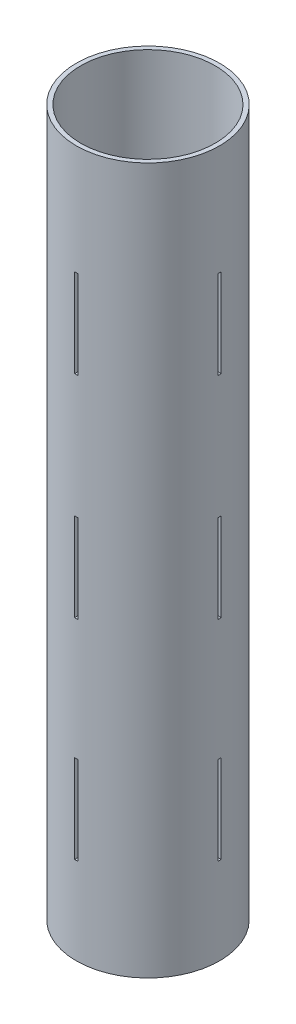
SolidWorks part; units mm, degrees
material "7075-T6 (SN)"
ref_plane "Front Plane" through (0, 0, 0) normal (0, 0, 1) x (1, 0, 0)
ref_plane "Top Plane" through (0, 0, 0) normal (0, 1, 0) x (1, 0, 0)
ref_plane "Right Plane" through (0, 0, 0) normal (1, 0, 0) x (0, 0, -1)
sketch "Sketch1" plane through (0, 0, 0) normal (0, 1, 0) x (1, 0, 0)
  circle A0 centre (0, 0) radius 32.5
  circle A1 centre (0, 0) radius 30.5
  dimension "D1" = 65
  dimension "D2" = 61
extrude "Boss-Extrude1" add sketch "Sketch1" along normal blind 320.25
sketch "Sketch2" plane through (0, 0, 0) normal (1, 0, 0) x (0, 0, -1)
  line L1 (0.75, 270.3798) -> (-0.75, 270.3798)
  line L2 (0.75, 270.3798) -> (0.75, 230.3798)
  line L3 (0.75, 230.3798) -> (-0.75, 230.3798)
  line L4 (-0.75, 270.3798) -> (-0.75, 230.3798)
  line L5 (0.75, 174.5) -> (-0.75, 174.5)
  line L6 (0.75, 174.5) -> (0.75, 134.5)
  line L7 (0.75, 134.5) -> (-0.75, 134.5)
  line L8 (-0.75, 174.5) -> (-0.75, 134.5)
  line L9 (0.75, 79.5) -> (-0.75, 79.5)
  line L10 (0.75, 79.5) -> (0.75, 39.5)
  line L11 (0.75, 39.5) -> (-0.75, 39.5)
  line L12 (-0.75, 79.5) -> (-0.75, 39.5)
extrude "Cut-Extrude1" cut sketch "Sketch2" against normal mid plane 100
sketch "Sketch3" plane through (0, 0, 0) normal (0, 0, 1) x (1, 0, 0)
  line L0 (0, 307.1688) -> (0, 342.7691) construction
  line L5 (-0.75, 230.3798) -> (0.75, 230.3798)
  line L6 (-0.75, 230.3798) -> (-0.75, 270.3798)
  line L7 (-0.75, 270.3798) -> (0.75, 270.3798)
  line L8 (0.75, 230.3798) -> (0.75, 270.3798)
  line L9 (-0.75, 134.5) -> (0.75, 134.5)
  line L10 (-0.75, 134.5) -> (-0.75, 174.5)
  line L11 (-0.75, 174.5) -> (0.75, 174.5)
  line L12 (0.75, 134.5) -> (0.75, 174.5)
  line L13 (-0.75, 39.5) -> (0.75, 39.5)
  line L14 (-0.75, 39.5) -> (-0.75, 79.5)
  line L15 (-0.75, 79.5) -> (0.75, 79.5)
  line L16 (0.75, 39.5) -> (0.75, 79.5)
extrude "Cut-Extrude2" cut sketch "Sketch3" against normal mid plane 100
ref_plane "Plane1" through (0, 0, 0) normal (-0.7071, 0, 0.7071) x (0.7071, 0, 0.7071)
ref_plane "Plane2" through (0, 0, 0) normal (0.7071, 0, 0.7071) x (0.7071, 0, -0.7071)
sketch "Sketch5" plane through (0, 0, 0) normal (-0.7071, 0, 0.7071) x (0.7071, 0, 0.7071)
  line L0 (0, 236.8549) -> (0, 26.8549) construction
  line L1 (9, 236.8549) -> (9, 26.8549)
  line L2 (-9, 236.8549) -> (-9, 26.8549)
  arc A0 (9, 236.8549) -> (-9, 236.8549) centre (0, 236.8549) ccw
  arc A1 (-9, 26.8549) -> (9, 26.8549) centre (0, 26.8549) ccw
  point P3 (0, 131.8549)
extrude "Cut-Extrude3" [suppressed] cut sketch "Sketch5" against normal mid plane 100 contours L1 A1 L2 A0
sketch "Sketch6" plane through (0, 0, 0) normal (0.7071, 0, 0.7071) x (0.7071, 0, -0.7071)
  line L0 (0, 236.8549) -> (0, 26.8549) construction
  line L1 (9, 236.8549) -> (9, 26.8549)
  line L2 (-9, 236.8549) -> (-9, 26.8549)
  arc A0 (9, 236.8549) -> (-9, 236.8549) centre (0, 236.8549) ccw
  arc A1 (-9, 26.8549) -> (9, 26.8549) centre (0, 26.8549) ccw
  point P3 (0, 131.8549)
extrude "Cut-Extrude4" [suppressed] cut sketch "Sketch6" against normal mid plane 100 contours L1 A1 L2 A0
